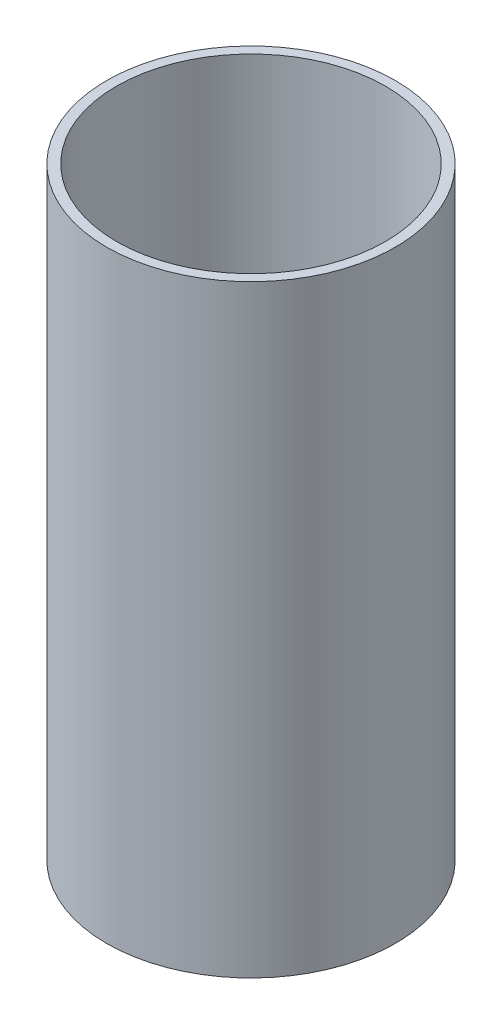
SolidWorks part; units mm, degrees
ref_plane "Front Plane" through (0, 0, 0) normal (0, 0, 1) x (1, 0, 0)
ref_plane "Top Plane" through (0, 0, 0) normal (0, 1, 0) x (1, 0, 0)
ref_plane "Right Plane" through (0, 0, 0) normal (1, 0, 0) x (0, 0, -1)
sketch "Sketch1" plane through (0, 0, 0) normal (0, 1, 0) x (1, 0, 0)
  circle A0 centre (0, 0) radius 17.85
  circle A1 centre (0, 0) radius 19.15
  dimension "D1" = 35.7
  dimension "D2" = 38.3
extrude "Boss-Extrude1" add sketch "Sketch1" along normal blind 80
